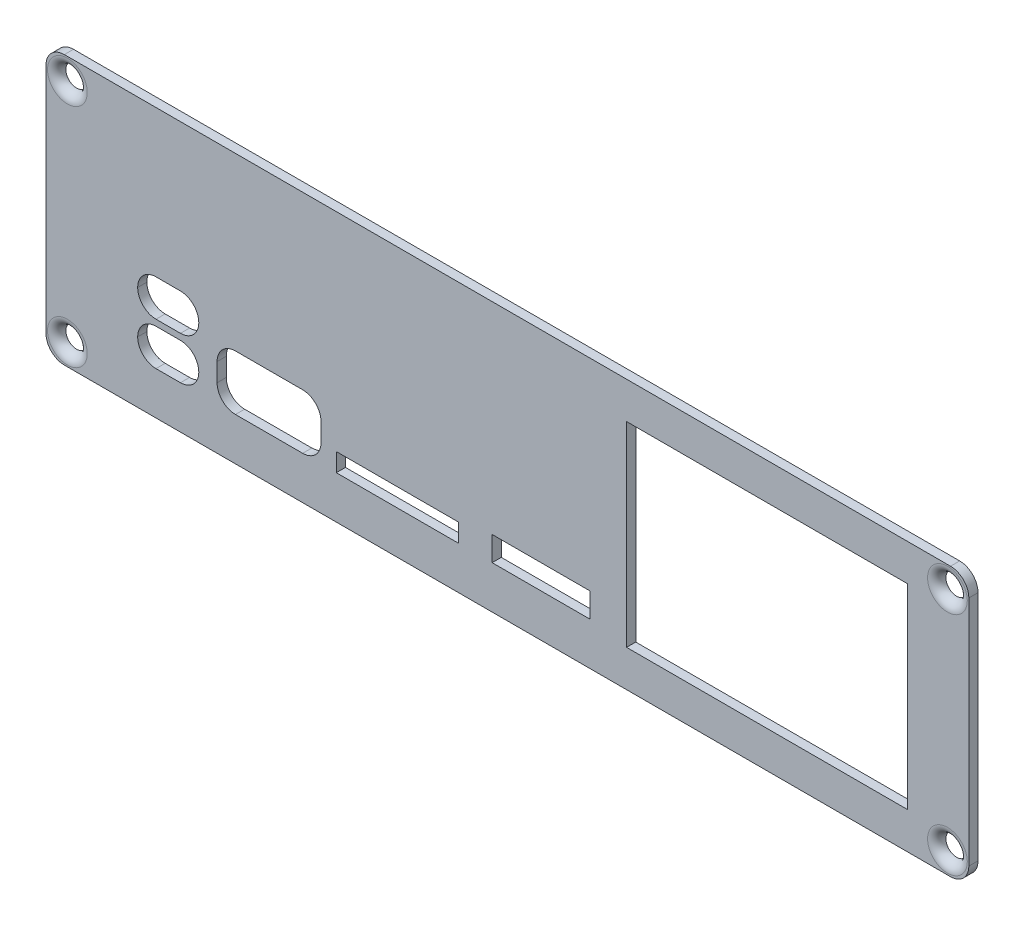
SolidWorks part; units mm, degrees
ref_plane "Front Plane" through (0, 0, 0) normal (0, 0, 1) x (1, 0, 0)
ref_plane "Top Plane" through (0, 0, 0) normal (0, 1, 0) x (1, 0, 0)
ref_plane "Right Plane" through (0, 0, 0) normal (1, 0, 0) x (0, 0, -1)
sketch "Sketch1" plane through (0, 0, 0) normal (0, 0, 1) x (1, 0, 0)
  line L1 (75.5, -22) -> (-75.5, -22)
  line L2 (75.5, -22) -> (75.5, 22)
  line L3 (75.5, 22) -> (-75.5, 22)
  line L4 (-75.5, -22) -> (-75.5, 22)
  line L5 (75.5, -22) -> (-75.5, 22) construction
  line L6 (75.5, 22) -> (-75.5, -22) construction
  point P0 (0, 0)
  dimension "D1" = 151
  dimension "D2" = 44
extrude "main_body" add sketch "Sketch1" along normal blind 1.5
fillet "body_corners" radius 3 4 edges at (-75.5, -22, 0.75) (75.5, -22, 0.75) (75.5, 22, 0.75) (-75.5, 22, 0.75)
sketch "Sketch2" plane through (0, 0, 1.5) normal (0, 0, 1) x (1, 0, 0)
  line L0 (-75.5, 18.5) -> (75.5, 18.5) construction
  line L1 (-75.5, 19) -> (-75.5, -19) construction
  line L2 (75.5, -19) -> (75.5, 19) construction
  line L3 (-72, 22) -> (-72, -22) construction
  line L4 (-75.5, -18.5) -> (75.5, -18.5) construction
  line L8 (72.5, 22) -> (-72.5, 22) construction
  line L9 (72, 22) -> (72, -22) construction
  line L10 (-72.5, -22) -> (72.5, -22) construction
  circle A1 centre (-72, -18.5) radius 1.75
  circle A2 centre (72, 18.5) radius 1.75
  circle A3 centre (72, -18.5) radius 1.75
  circle A4 centre (-72, 18.5) radius 1.75
  dimension "D5" = 3.5
  dimension "D6" = 3.5
  dimension "D7" = 3.5
  dimension "D8" = 3.5
  dimension "D1" = 3.5
  dimension "D2" = 3.5
  dimension "D3" = 3.5
  dimension "D4" = 3.5
extrude "mounting_holes" cut sketch "Sketch2" against normal blind 1.5
fillet "bolt_heads" radius 1.5 4 edges at (-70.25, 18.5, 1.5) (-70.25, -18.5, 1.5) (73.75, -18.5, 1.5) (73.75, 18.5, 1.5)
sketch "Sketch3" plane through (0, 0, 1.5) normal (0, 0, 1) x (1, 0, 0)
  line L0 (-75.5, 5) -> (75.5, 5) construction
  line L1 (-75.5, 19) -> (-75.5, -19) construction
  line L2 (75.5, -19) -> (75.5, 19) construction
  line L3 (72.5, 22) -> (-72.5, 22) construction
  line L4 (-72.5, -22) -> (72.5, -22) construction
  line L5 (0, 22) -> (0, -22) construction
  line L7 (19.5, 16) -> (65.5, 16)
  line L8 (-60.5, -2) -> (-50.5, -2)
  line L9 (19.5, 16) -> (19.5, -16)
  line L10 (-60.5, -2) -> (-60.5, -8)
  line L11 (-60.5, -8) -> (-50.5, -8)
  line L12 (19.5, -16) -> (65.5, -16)
  line L13 (-50.5, -2) -> (-50.5, -8)
  line L14 (-60.5, -2) -> (-50.5, -8) construction
  line L15 (65.5, 16) -> (65.5, -16)
  line L16 (-60.5, -8) -> (-50.5, -2) construction
  line L17 (-47.5, -6) -> (-30.5, -6)
  line L18 (-47.5, -6) -> (-47.5, -15)
  line L19 (-47.5, -15) -> (-30.5, -15)
  line L20 (-30.5, -6) -> (-30.5, -15)
  line L21 (-47.5, -6) -> (-30.5, -15) construction
  line L22 (-47.5, -15) -> (-30.5, -6) construction
  line L23 (-60.5, -9) -> (-50.5, -9)
  line L24 (-60.5, -9) -> (-60.5, -15)
  line L25 (-60.5, -15) -> (-50.5, -15)
  line L26 (-50.5, -9) -> (-50.5, -15)
  line L27 (-60.5, -9) -> (-50.5, -15) construction
  line L28 (-60.5, -15) -> (-50.5, -9) construction
  line L29 (-28, -12) -> (-8, -12)
  line L30 (-28, -12) -> (-28, -15)
  line L31 (-28, -15) -> (-8, -15)
  line L32 (-8, -12) -> (-8, -15)
  line L33 (-28, -12) -> (-8, -15) construction
  line L34 (-28, -15) -> (-8, -12) construction
  line L35 (-2.5, -11) -> (13.5, -11)
  line L36 (-2.5, -11) -> (-2.5, -15)
  line L37 (-2.5, -15) -> (13.5, -15)
  line L38 (13.5, -11) -> (13.5, -15)
  line L39 (-2.5, -11) -> (13.5, -15) construction
  line L40 (-2.5, -15) -> (13.5, -11) construction
  line L41 (19.5, 16) -> (65.5, -16) construction
  line L42 (19.5, -16) -> (65.5, 16) construction
  point P12 (42.5, 0)
  point P15 (5.5, -13)
  point P34 (-55.5, -12)
  point P36 (-55.5, -5)
  point P41 (-39, -10.5)
  point P49 (-55.5, -15)
  point P50 (-60.5, -12)
  point P51 (-18, -13.5)
  dimension "D7" = 73
  dimension "D8" = 7
  dimension "D9" = 4
  dimension "D10" = 16
  dimension "D11" = 46
  dimension "D12" = 55.5
  dimension "D13" = 6
  dimension "D14" = 10
  dimension "D15" = 39
  dimension "D1" = 17
  dimension "D4" = 10
  dimension "D5" = 6
  dimension "D6" = 32
  dimension "D16" = 7
  dimension "D17" = 18
  dimension "D18" = 5.5
  dimension "D19" = 10
  dimension "D20" = 6
  dimension "D21" = 17
  dimension "D22" = 9
  dimension "D23" = 15
  dimension "D24" = 28
  dimension "D25" = 14
  dimension "D26" = 7
  dimension "D27" = 15
  dimension "D28" = 7
  dimension "D29" = 47.5
  dimension "D30" = 3
  dimension "D31" = 20
  dimension "D32" = 19.5
extrude "connectors" cut sketch "Sketch3" against normal blind 1.5
fillet "usb_host_corners" radius 3 4 edges at (-30.5, -15, 0.75) (-30.5, -6, 0.75) (-47.5, -15, 0.75) (-47.5, -6, 0.75)
fillet "usb_dfu_corners" radius 3 8 edges at (-50.5, -2, 0.75) (-50.5, -8, 0.75) (-60.5, -8, 0.75) (-60.5, -2, 0.75) (-50.5, -9, 0.75) (-50.5, -15, 0.75) (-60.5, -15, 0.75) (-60.5, -9, 0.75)
